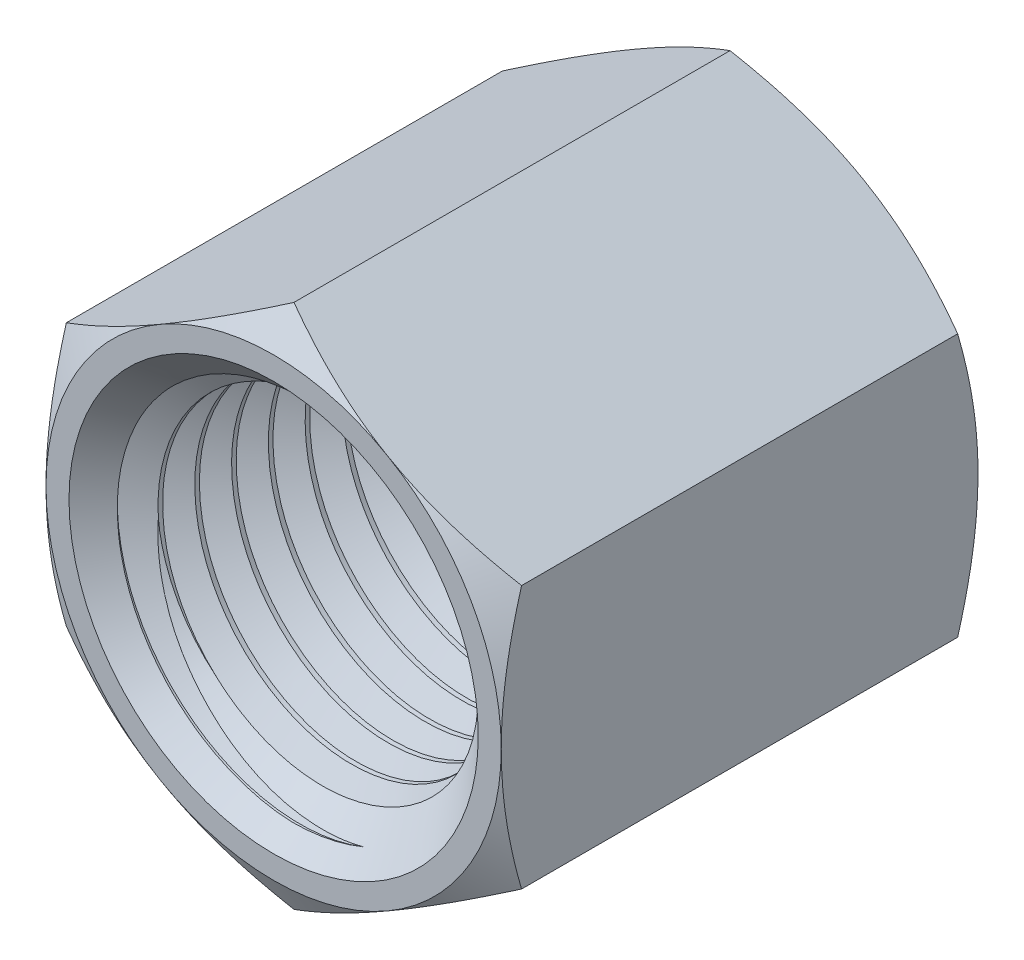
SolidWorks part; units mm, degrees
ref_plane "Front Plane" through (0, 0, 0) normal (0, 0, 1) x (1, 0, 0)
ref_plane "Top Plane" through (0, 0, 0) normal (0, 1, 0) x (1, 0, 0)
ref_plane "Right Plane" through (0, 0, 0) normal (1, 0, 0) x (0, 0, -1)
sketch "Sketch1" plane through (0, 0, 0) normal (1, 0, 0) x (0, 0, -1)
  line L0 (-9.144, 0) -> (9.144, 0) construction
  line L1 (-9.144, 7.1437) -> (-9.144, -7.1437) construction
  line L2 (0, -8.7312) -> (0, 8.7312) construction
  line L3 (9.144, 5.588) -> (9.144, -5.588) construction
  line L4 (-9.144, 7.1437) -> (-10.5551, 7.1437) construction
  line L5 (-9.144, 8.7312) -> (9.144, 8.7312) construction
  line L6 (0, 7.1437) -> (2.286, 7.1437) construction
  line L7 (2.286, 7.1437) -> (4.572, 7.1437) construction
  line L8 (4.572, 7.1437) -> (6.858, 7.1437) construction
  line L9 (6.858, 7.1437) -> (9.144, 7.1437) construction
  line L10 (-9.144, 7.1437) -> (0, 7.1437) construction
  line L11 (2.286, 7.1437) -> (6.858, 5.588) construction
  line L12 (6.858, 5.588) -> (9.144, 5.588) construction
  line L13 (-9.144, -7.1437) -> (0, -7.1437) construction
  line L14 (0, -7.1437) -> (2.286, -7.1437) construction
  line L15 (2.286, -7.1437) -> (6.858, -5.588) construction
  line L16 (6.858, -5.588) -> (9.144, -5.588) construction
  point P2 (0, 0)
  point P6 (-9.144, 0)
  point P9 (0, 0)
  point P12 (9.144, 0)
  point P15 (0, 8.7312)
  point P17 (9.144, -5.588)
  dimension "Tube" = 11.176
  dimension "Thread" = 14.2875
  dimension "Hex" = 17.4625
  dimension "Length" = 18.288
  dimension "Pitch" = 1.4111
sketch "Sketch1A" plane through (0, 0, 0) normal (0, 0, 1) x (1, 0, 0)
  line L0 (-5.588, 0) -> (5.588, 0) construction
  line L1 (0, 10.082) -> (-8.7313, 5.041) construction
  line L2 (-8.7313, 5.041) -> (-8.7313, -5.041) construction
  line L3 (-8.7313, -5.041) -> (0, -10.082) construction
  line L4 (0, -10.082) -> (8.7312, -5.041) construction
  line L5 (8.7312, -5.041) -> (8.7312, 5.041) construction
  line L6 (8.7312, 5.041) -> (0, 10.082) construction
  line L7 (0, 5.588) -> (0, -5.588) construction
  line L8 (0, -8.7312) -> (0, 8.7312) construction
  circle A0 centre (0, 0) radius 8.7312 construction
  point P1 (0, 0)
  point P15 (0, -7.1437)
ref_plane "Plane1" through (0, 0, 9.144) normal (0, 0, 1) x (1, 0, 0)
sketch "Sketch2" plane through (0, 0, 0) normal (0, 0, 1) x (1, 0, 0)
  line L0 (0, 5.588) -> (0, -5.588) construction
  line L1 (0, 10.082) -> (-8.7312, 5.041)
  line L2 (-8.7312, 5.041) -> (-8.7313, -5.041)
  line L3 (-8.7313, -5.041) -> (0, -10.082)
  line L4 (0, -10.082) -> (8.7312, -5.041)
  line L5 (8.7312, -5.041) -> (8.7313, 5.041)
  line L6 (8.7313, 5.041) -> (0, 10.082)
  circle A0 centre (0, 0) radius 8.7312 construction
  circle A1 centre (0, 0) radius 5.588
extrude "Boss-Extrude1" add sketch "Sketch2" along normal up to vertex (9.144 mm away) and the other way up to vertex (9.144 mm away) up to point (0, 0, 9.144) other way up to point (0, 0, -9.144)
sketch "Sketch3" plane through (0, 0, 0) normal (1, 0, 0) x (0, 0, -1)
  line L0 (-9.144, 7.1437) -> (0, 7.1438) construction
  line L1 (0, -8.7312) -> (0, 8.7312) construction
  line L2 (0, 7.1438) -> (2.286, 7.1438) construction
  line L3 (2.286, 7.1438) -> (4.572, 7.1438) construction
  line L4 (4.572, 7.1438) -> (6.858, 7.1437) construction
  line L5 (6.858, 7.1437) -> (9.144, 7.1437) construction
  line L6 (9.144, 5.041) -> (9.144, 10.082) construction
  line L7 (-9.144, 7.1437) -> (2.286, 7.1438)
  line L8 (2.286, 7.1438) -> (6.858, 5.588)
  line L9 (6.858, 5.588) -> (9.144, 5.588)
  line L10 (-9.144, 7.1437) -> (-9.144, 0)
  line L11 (-9.144, 0) -> (9.144, 0)
  line L12 (9.144, 0) -> (9.144, 5.588)
revolve "Cut-Revolve1" cut sketch "Sketch3" angle 360 about L11
sketch "Sketch4" plane through (0, 0, 9.144) normal (0, 0, 1) x (1, 0, 0)
  circle A0 centre (0, 0) radius 8.7312
extrude "Cut-Extrude1" cut sketch "Sketch4" against normal blind 2.54 draft 60 flip side to cut
mirror "Mirror1" about plane through (0, 0, 0) normal (0, 0, 1) of "Cut-Extrude1"
sketch "Sketch5" plane through (0, 0, 9.144) normal (0, 0, 1) x (1, 0, 0)
  circle A0 centre (0, 0) radius 7.1438
curve "Helix/Spiral1" pitch 1.4111 height 13.716 radius 7.1438 centre (0, 0, 9.144) axis (0, 0, -1) start towards (0, 1, 0)
sketch "Sketch6" plane through (0, 0, 0) normal (1, 0, 0) x (0, 0, -1)
  line L0 (-10.511, 7.2201) -> (-9.0999, 7.2201) construction
  line L1 (-9.0999, 7.2201) -> (-9.8055, 5.9981) construction
  line L2 (-9.8055, 5.9981) -> (-10.511, 7.2201) construction
  line L3 (-9.8055, 5.9981) -> (-9.8055, 6.1508) construction
  line L4 (-9.8055, 6.1508) -> (-9.8055, 7.0674) construction
  line L5 (-9.8055, 7.0674) -> (-9.8055, 7.2201) construction
  line L6 (-9.8937, 6.1508) -> (-9.7173, 6.1508) construction
  line L7 (-9.144, 7.1437) -> (-9.7173, 6.1508)
  line L8 (-9.1881, 7.0674) -> (-10.4228, 7.0674) construction
  line L9 (-9.7173, 6.1508) -> (-9.8937, 6.1508)
  line L10 (-9.144, 7.1437) -> (-10.4669, 7.1437) construction
  line L11 (-9.8937, 6.1508) -> (-10.4669, 7.1437)
  line L12 (-10.4669, 7.1437) -> (-9.144, 7.1437)
  point P12 (-9.8055, 6.1508)
  point P14 (-9.8055, 7.0674)
  point P15 (-9.8055, 7.1438)
  point P16 (-9.8055, 7.1438)
  dimension "D1" = 1.4111
  dimension "D2" = 0.1764
sweep "Sweep1" add profiles "Sketch6" path "Helix/Spiral1"
sketch "Sketch7" plane through (0, 0, 9.144) normal (0, 0, 1) x (1, 0, 0)
  circle A0 centre (0, 0) radius 7.8493
  dimension "D1" = 15.6986
extrude "Cut-Extrude2" cut sketch "Sketch7" against normal blind 2.54 draft 45 and the other way through all
equation "\"D3@Helix/Spiral1\"=\"Length@Sketch1\"*.75"
equation "\"D4@Helix/Spiral1\"=\"Pitch@Sketch1\""
equation "\"D1@Sketch6\"=\"Pitch@Sketch1\""
equation "\"D2@Sketch6\"=\"D1@Sketch6\"/8"
equation "\"D1@Sketch7\"=\"Thread@Sketch1\"+\"Pitch@Sketch1\""
